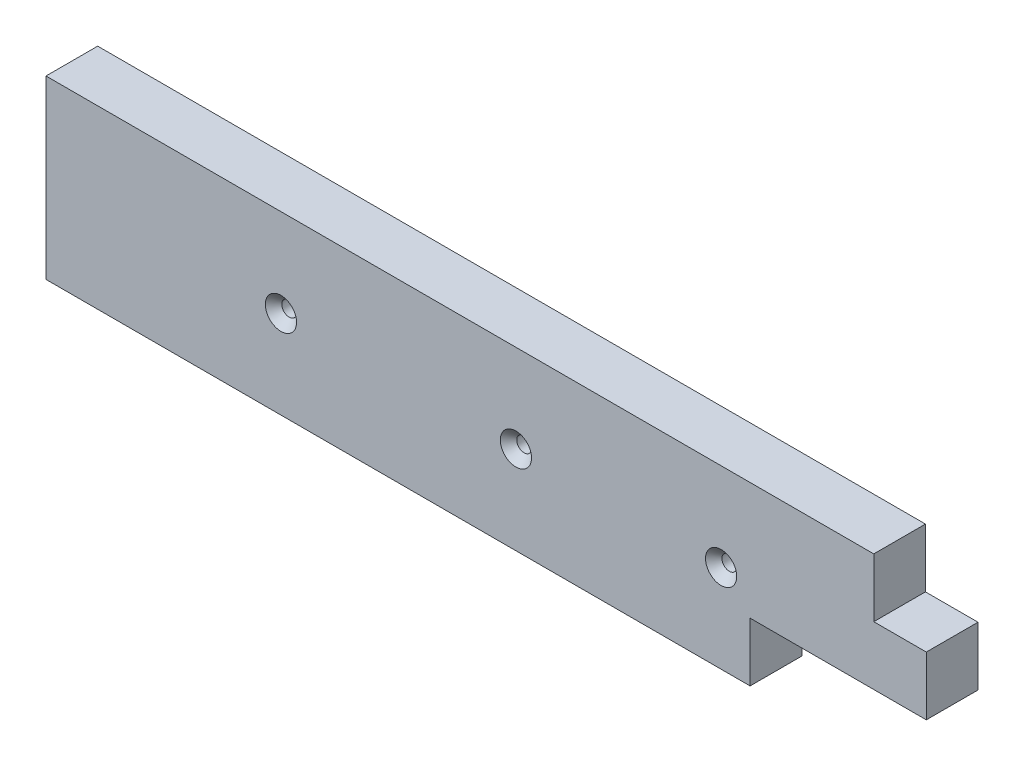
SolidWorks part; units mm, degrees
ref_plane "Front Plane" through (0, 0, 0) normal (0, 0, 1) x (1, 0, 0)
ref_plane "Top Plane" through (0, 0, 0) normal (0, 1, 0) x (1, 0, 0)
ref_plane "Right Plane" through (0, 0, 0) normal (1, 0, 0) x (0, 0, -1)
sketch "Sketch1" plane through (0, 0, 0) normal (0, 1, 0) x (1, 0, 0)
  line L1 (-190.3259, -11.176) -> (190.3259, -11.176)
  line L2 (-190.3259, -11.176) -> (-190.3259, 11.176)
  line L3 (-190.3259, 11.176) -> (190.3259, 11.176)
  line L4 (190.3259, -11.176) -> (190.3259, 11.176)
  line L5 (-190.3259, -11.176) -> (190.3259, 11.176) construction
  line L6 (-190.3259, 11.176) -> (190.3259, -11.176) construction
  point P0 (0, 0)
extrude "Boss-Extrude1" add sketch "Sketch1" along normal mid plane 76.2 contours L1 L4 L3 L2
sketch "Sketch3" plane through (0, 0, 11.176) normal (0, 0, 1) x (1, 0, 0)
  line L1 (167.6064, 12.7) -> (190.3259, 12.7)
  line L2 (190.3259, 38.1) -> (190.3259, 12.7)
  line L3 (167.6064, 12.7) -> (167.6064, 38.1)
  line L4 (167.6064, 38.1) -> (190.3259, 38.1)
  line L5 (114.1259, -12.7) -> (190.3259, -12.7)
  line L6 (114.1259, -12.7) -> (114.1259, -38.1)
  line L7 (114.1259, -38.1) -> (190.3259, -38.1)
  line L8 (190.3259, -12.7) -> (190.3259, -38.1)
  dimension "D1" = 76.2
  dimension "D2" = 25.4
hole_wizard "CSK for M6 Hex Socket Countersunk Head Screw6" positions "Sketch21" profile "Sketch20" countersink size "M6" standard "Lanco STD" end condition through all
sketch "Sketch21" plane through (0, 0, 11.176) normal (0, 0, 1) x (1, 0, 0)
  line L0 (-190.3259, 38.1) -> (-190.3259, -38.1) construction
  point P0 (-88.7259, 0)
  point P3 (-190.3259, 0)
  dimension "D1" = 101.6
sketch "Sketch20" plane through (-88.7259, 0, 11.176) normal (1, 0, 0) x (0, -1, 0)
  line L0 (0, 0) -> (0, 22.352)
  line L1 (0, 22.352) -> (3.2, 22.352)
  line L2 (3.2, 22.352) -> (3.2, 3.55)
  line L3 (3.2, 3.55) -> (6.75, 0)
  line L5 (6.75, 0) -> (0, 0)
  line L6 (-3.2, 3.55) -> (-6.75, 0) construction
  line L11 (0, -6.35) -> (0, 107.95) construction
  dimension "Thru Hole Dia." = 6.4
  dimension "Thru Hole Depth" = 22.352
  dimension "Near C'Sink Dia." = 13.5
  dimension "Near C'Sink Angle" = 90
hole_wizard "CSK for M6 Hex Socket Countersunk Head Screw7" positions "Sketch23" profile "Sketch22" countersink size "M6" standard "Lanco STD" end condition through all
sketch "Sketch23" plane through (0, 0, 11.176) normal (0, 0, 1) x (1, 0, 0)
  line L1 (-190.3259, 38.1) -> (-190.3259, -38.1) construction
  point P0 (12.8741, 0)
  point P5 (-190.3259, 0)
  dimension "D1" = 203.2
sketch "Sketch22" plane through (12.8741, 0, 11.176) normal (1, 0, 0) x (0, -1, 0)
  line L0 (0, 0) -> (0, 22.352)
  line L1 (0, 22.352) -> (3.2, 22.352)
  line L2 (3.2, 22.352) -> (3.2, 3.55)
  line L3 (3.2, 3.55) -> (6.75, 0)
  line L5 (6.75, 0) -> (0, 0)
  line L6 (-3.2, 3.55) -> (-6.75, 0) construction
  line L11 (0, -6.35) -> (0, 107.95) construction
  dimension "Thru Hole Dia." = 6.4
  dimension "Thru Hole Depth" = 22.352
  dimension "Near C'Sink Dia." = 13.5
  dimension "Near C'Sink Angle" = 90
hole_wizard "CSK for M6 Hex Socket Countersunk Head Screw8" positions "Sketch25" profile "Sketch24" countersink size "M6" standard "Lanco STD" end condition through all
sketch "Sketch25" plane through (0, 0, 11.176) normal (0, 0, 1) x (1, 0, 0)
  point P0 (101.6, 0)
  dimension "D1" = 101.6
sketch "Sketch24" plane through (101.6, 0, 11.176) normal (1, 0, 0) x (0, -1, 0)
  line L0 (0, 0) -> (0, 22.352)
  line L1 (0, 22.352) -> (3.2, 22.352)
  line L2 (3.2, 22.352) -> (3.2, 3.55)
  line L3 (3.2, 3.55) -> (6.75, 0)
  line L5 (6.75, 0) -> (0, 0)
  line L6 (-3.2, 3.55) -> (-6.75, 0) construction
  line L11 (0, -6.35) -> (0, 107.95) construction
  dimension "Thru Hole Dia." = 6.4
  dimension "Thru Hole Depth" = 22.352
  dimension "Near C'Sink Dia." = 13.5
  dimension "Near C'Sink Angle" = 90
extrude "Cut-Extrude1" cut sketch "Sketch3" against normal through all
